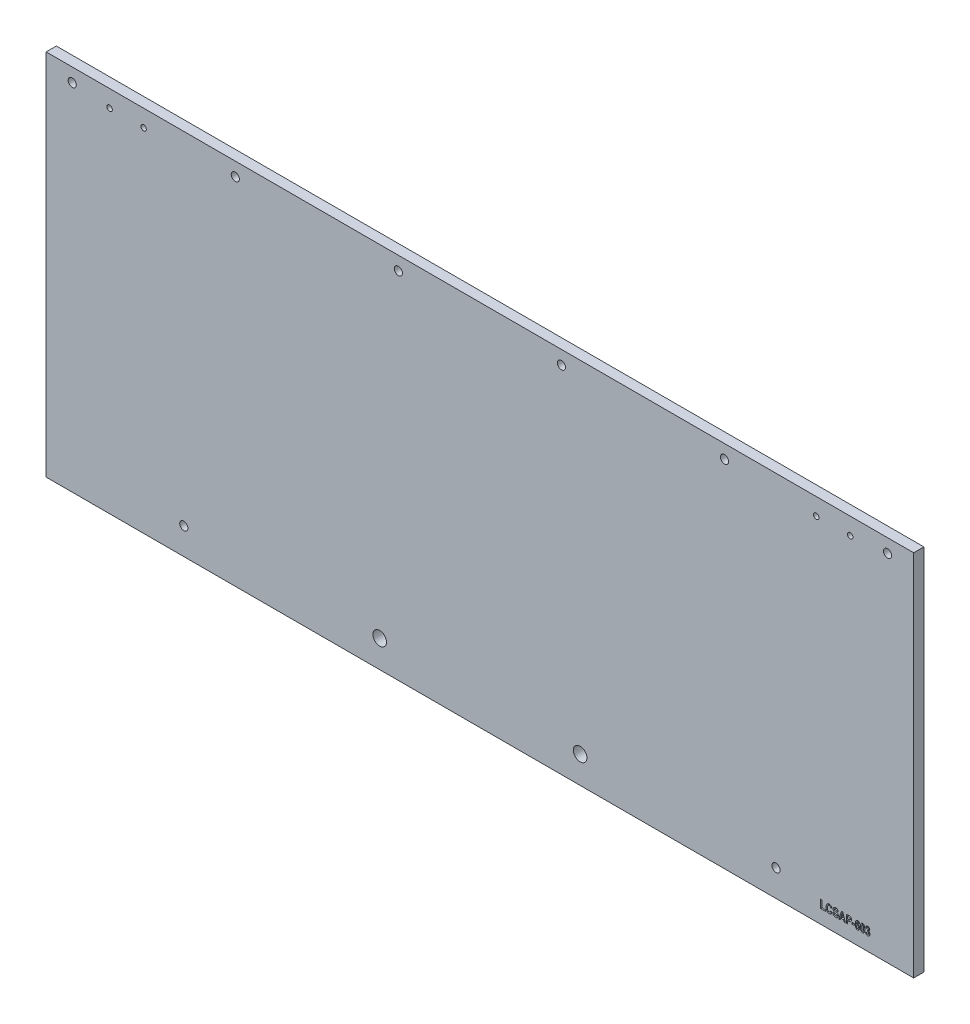
SolidWorks part; units mm, degrees
ref_plane "Front (1)" through (0, 0, 0) normal (0, 0, 1) x (1, 0, 0)
ref_plane "Top (2)" through (0, 0, 0) normal (0, 1, 0) x (1, 0, 0)
ref_plane "Right (3)" through (0, 0, 0) normal (1, 0, 0) x (0, 0, -1)
ref_axis "X-Axis" through (-80.9, 0, 0) along (1, 0, 0)
ref_axis "Y-Axis" through (0, -50, 0) along (0, 1, 0)
ref_axis "Z-Axis" through (0, 0, 50) along (0, 0, -1)
sketch "Sketch1" plane through (0, 0, 0) normal (0, 0, 1) x (1, 0, 0)
  line L1 (0, 0) -> (405.384, 0)
  line L2 (0, 0) -> (0, 172.085)
  line L3 (0, 172.085) -> (405.384, 172.085)
  line L4 (405.384, 0) -> (405.384, 172.085)
  dimension "D1" = 405.384
  dimension "D2" = 172.085
extrude "Boss-Extrude1" add sketch "Sketch1" along normal blind 4.7625
sketch "Sketch2" plane through (0, 0, 4.7625) normal (0, 0, 1) x (1, 0, 0)
  line L2 (64.3255, 12.4333) -> (341.0585, 12.4333) construction
  line L4 (29.6545, 164.1475) -> (375.7295, 164.1475) construction
  line L6 (202.692, 12.4333) -> (202.692, 172.085) construction
  line L7 (405.384, 172.085) -> (0, 172.085) construction
  line L11 (405.384, 172.085) -> (0, 172.085) construction
  circle A0 centre (29.6545, 164.1475) radius 1.27
  circle A1 centre (45.5295, 164.1475) radius 1.27
  circle A2 centre (359.8545, 164.1475) radius 1.27
  circle A3 centre (375.7295, 164.1475) radius 1.27
  circle A4 centre (64.3255, 12.4333) radius 1.905
  circle A5 centre (341.0585, 12.4333) radius 1.905
  point P16 (202.692, 164.1475)
  dimension "D9" = 2.54
  dimension "D10" = 3.81
  dimension "D6" = 7.9375
  dimension "D1" = 15.875
  dimension "D2" = 15.875
  dimension "D3" = 314.325
  dimension "D4" = 159.6517
  dimension "D5" = 276.733
extrude "Cut-Extrude1" cut sketch "Sketch2" against normal through all
sketch "Sketch3" plane through (0, 0, 0) normal (0, 0, -1) x (-1, 0, 0)
  line L0 (-405.384, 0) -> (-405.384, 172.085) construction
  line L1 (-249.5233, 12.7) -> (-202.692, 0) construction
  line L2 (0, 0) -> (-405.384, 0) construction
  line L3 (-202.692, 0) -> (-155.8608, 12.7) construction
  line L4 (-405.384, 172.085) -> (0, 172.085) construction
  circle A0 centre (-249.5233, 12.7) radius 3.175
  circle A1 centre (-155.8608, 12.7) radius 3.175
  circle A2 centre (-393.192, 165.735) radius 1.905
  circle A3 centre (-316.992, 165.735) radius 1.905
  circle A4 centre (-240.792, 165.735) radius 1.905
  circle A5 centre (-164.592, 165.735) radius 1.905
  circle A6 centre (-88.392, 165.735) radius 1.905
  circle A7 centre (-12.192, 165.735) radius 1.905
  dimension "D1" = 6.35
  dimension "D6" = 3.81
  dimension "D2" = 93.6625
  dimension "D3" = 12.7
  dimension "D4" = 12.192
  dimension "D5" = 6.35
  dimension "D8" = 76.2
  dimension "D7" = 6
extrude "Cut-Extrude2" cut sketch "Sketch3" against normal through all
sketch "Sketch4" plane through (0, 0, 4.7625) normal (0, 0, 1) x (1, 0, 0)
  line L0 (405.384, 6.35) -> (341.884, 6.35) construction
  line L1 (405.384, 0) -> (405.384, 172.085) construction
  line L2 (0, 0) -> (405.384, 0) construction
  text T0 "<b>LCSAP-603</b>"
  dimension "D1" = 6.35
  dimension "D2" = 63.5
extrude "Cut-Extrude3" cut sketch "Sketch4" against normal blind 1.016
